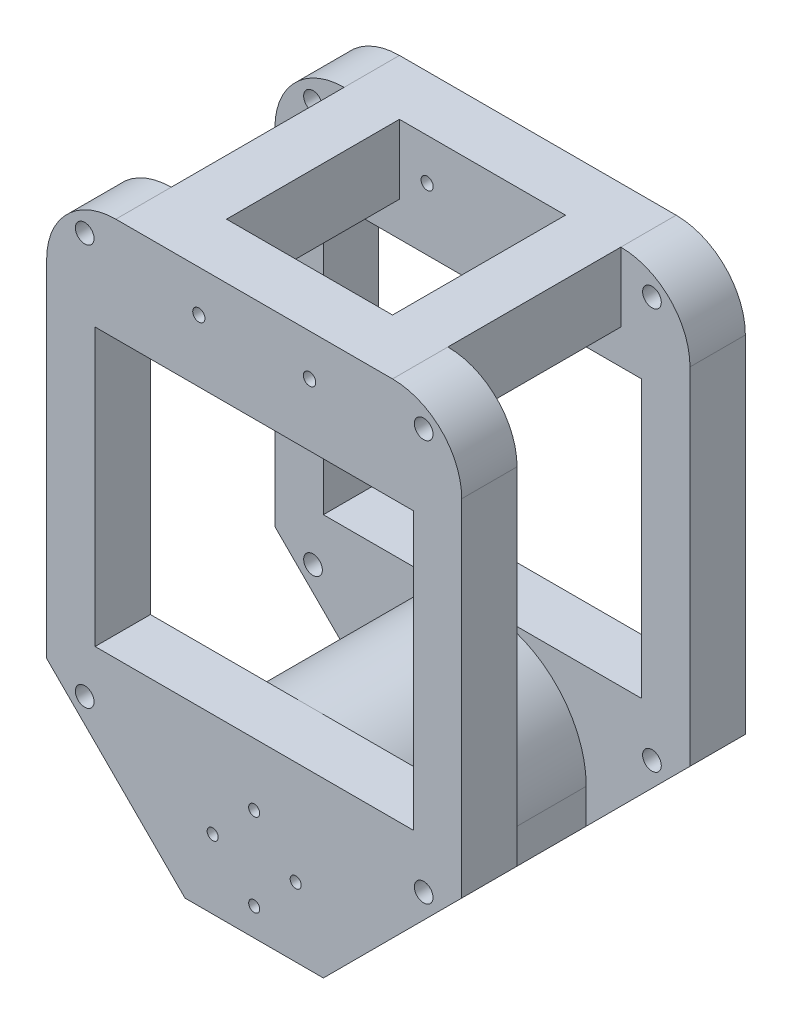
SolidWorks part; units mm, degrees
ref_plane "Front Plane" through (0, 0, 0) normal (0, 0, 1) x (1, 0, 0)
ref_plane "Top Plane" through (0, 0, 0) normal (0, 1, 0) x (1, 0, 0)
ref_plane "Right Plane" through (0, 0, 0) normal (1, 0, 0) x (0, 0, -1)
sketch "Sketch1" plane through (0, 0, 0) normal (0, 0, 1) x (1, 0, 0)
  line L11 (-30, 20.2064) -> (0, 20.2064)
  line L12 (0, 20.2064) -> (30, 20.2064)
  line L13 (30, 20.2064) -> (30, -59.7936)
  line L14 (30, -59.7936) -> (-30, -59.7936)
  line L15 (-30, -59.7936) -> (-30, 20.2064)
  circle A0 centre (-8, 14.2064) radius 0.8836
  circle A1 centre (8, 14.2064) radius 0.8966
  circle A2 centre (0, -49.7936) radius 8 construction
  circle A3 centre (0, -49.7936) radius 6 construction
  circle A4 centre (0, -43.7936) radius 0.8
  circle A5 centre (6, -49.7936) radius 0.8
  circle A6 centre (0, -55.7936) radius 0.8
  circle A7 centre (-6, -49.7936) radius 0.8
  circle A8 centre (-24.5, 16.2064) radius 1.35
  circle A9 centre (24.5, 16.2064) radius 1.35
  circle A10 centre (-24.5, -41.7936) radius 1.35
  circle A11 centre (24.5, -41.7936) radius 1.35
  point P25 (0, -49.7936)
  dimension "D7" = 4
  dimension "D10" = 49
  dimension "D1" = 8
  dimension "D2" = 30
  dimension "D3" = 30
  dimension "D4" = 16
  dimension "D5" = 0
  dimension "D6" = 80
  dimension "D8" = 10
  dimension "D9" = 6
  dimension "D11" = 24.5
  dimension "D12" = 58
  dimension "D13" = 4
extrude "Boss-Extrude1" add sketch "Sketch1" along normal blind 8
sketch "Sketch2" plane through (0, 0, 8) normal (0, 0, 1) x (1, 0, 0)
  line L0 (-12, 20.2064) -> (-12, 10.2064)
  line L1 (30, 20.2064) -> (-30, 20.2064) construction
  line L2 (12, 20.2064) -> (12, 10.2064)
  line L3 (12, 20.2064) -> (20, 20.2064)
  line L4 (20, 20.2064) -> (20, 10.2064)
  line L5 (20, 10.2064) -> (12, 10.2064)
  line L6 (-12, 20.2064) -> (-20, 20.2064)
  line L7 (-20, 20.2064) -> (-20, 10.2064)
  line L8 (-20, 10.2064) -> (-12, 10.2064)
  dimension "D1" = 12
  dimension "D2" = 12
  dimension "D3" = 10
  dimension "D4" = 8
  dimension "D5" = 8
extrude "Boss-Extrude3" add sketch "Sketch2" along normal blind 25
extrude "Boss-Extrude4" add sketch "Sketch1<2>" against normal blind 8 from offset 41
sketch "Sketch1<2>" plane through (0, 0, 0) normal (0, 0, 1) x (1, 0, 0) same geometry as "Sketch1"
sketch "Sketch3" plane through (0, 0, 8) normal (0, 0, 1) x (1, 0, 0)
  line L4 (-30, -59.7936) -> (-10, -59.7936) construction
  line L5 (-6, -49.7936) -> (6, -49.7936) construction
  line L6 (-10, -49.7936) -> (-10, -59.7936)
  line L7 (0, -43.7936) -> (0, -55.7936) construction
  line L8 (10, -49.7936) -> (10, -59.7936)
  line L9 (10, -59.7936) -> (30, -59.7936) construction
  line L10 (-10, -59.7936) -> (10, -59.7936)
  arc A1 (10, -49.7936) -> (-10, -49.7936) centre (0, -49.7936) ccw
extrude "Cut-Extrude1" cut sketch "Sketch3" against normal blind 3
extrude "Cut-Extrude2" cut sketch "Sketch3<2>" along normal blind 3 from surface starting at face at (25.85, -41.7936, 33)
sketch "Sketch3<2>" plane through (0, 0, 8) normal (0, 0, 1) x (1, 0, 0) same geometry as "Sketch3"
sketch "Sketch4" plane through (0, 0, 33) normal (0, 0, -1) x (-1, 0, 0)
  line L0 (-15, -49.7936) -> (-15, -59.7936)
  line L1 (15, -49.7936) -> (15, -59.7936)
  line L2 (-10, -49.7936) -> (-10, -59.7936)
  line L3 (15, -59.7936) -> (30, -59.7936)
  line L4 (-15, -59.7936) -> (-10, -59.7936)
  line L5 (10, -49.7936) -> (10, -59.7936)
  line L6 (-15, -59.7936) -> (-10, -59.7936)
  line L7 (10, -59.7936) -> (15, -59.7936)
  line L8 (15, -59.7936) -> (10, -59.7936)
  line L10 (-15, -59.7936) -> (-10, -59.7936)
  line L11 (10, -59.7936) -> (15, -59.7936)
  line L15 (-30, -59.7936) -> (-10, -59.7936)
  line L16 (-10, -59.7936) -> (-10, -49.7936)
  line L17 (10, -49.7936) -> (10, -59.7936)
  line L18 (10, -59.7936) -> (30, -59.7936)
  line L19 (30, -59.7936) -> (30, 20.2064)
  line L20 (30, 20.2064) -> (20, 20.2064)
  line L21 (20, 20.2064) -> (20, 10.2064)
  line L22 (20, 10.2064) -> (12, 10.2064)
  line L23 (12, 10.2064) -> (12, 20.2064)
  line L24 (12, 20.2064) -> (-12, 20.2064)
  line L25 (-12, 20.2064) -> (-12, 10.2064)
  line L26 (-12, 10.2064) -> (-20, 10.2064)
  line L27 (-20, 10.2064) -> (-20, 20.2064)
  line L28 (-20, 20.2064) -> (-30, 20.2064)
  line L29 (-30, 20.2064) -> (-30, -59.7936)
  line L30 (-30, -59.7936) -> (-15, -59.7936)
  line L34 (30, -59.7936) -> (30, 20.2064)
  line L35 (30, 20.2064) -> (20, 20.2064)
  line L36 (20, 20.2064) -> (20, 10.2064)
  line L37 (20, 10.2064) -> (12, 10.2064)
  line L38 (12, 10.2064) -> (12, 20.2064)
  line L39 (12, 20.2064) -> (-12, 20.2064)
  line L40 (-12, 20.2064) -> (-12, 10.2064)
  line L41 (-12, 10.2064) -> (-20, 10.2064)
  line L42 (-20, 10.2064) -> (-20, 20.2064)
  line L43 (-20, 20.2064) -> (-30, 20.2064)
  line L44 (-30, 20.2064) -> (-30, -59.7936)
  arc A0 (15, -49.7936) -> (-15, -49.7936) centre (0, -49.7936) ccw
  arc A1 (10, -49.7936) -> (-10, -49.7936) centre (0, -49.7936) ccw
  arc A2 (10, -49.7936) -> (-10, -49.7936) centre (0, -49.7936) ccw
  arc A3 (10, -49.7936) -> (-10, -49.7936) centre (0, -49.7936) ccw
  arc A4 (-10, -49.7936) -> (9.3304, -53.3913) centre (0, -49.7936) cw
  dimension "D1" = 0
sketch "Sketch5" plane through (0, 0, 33) normal (0, 0, -1) x (-1, 0, 0)
  line L0 (-15, -49.7936) -> (-15, -59.7936)
  line L1 (-15, -59.7936) -> (-10, -59.7936)
  line L2 (-10, -59.7936) -> (-10, -49.7936)
  line L3 (10, -49.7936) -> (10, -59.7936)
  line L4 (10, -59.7936) -> (15, -59.7936)
  line L5 (15, -59.7936) -> (15, -49.7936)
  arc A0 (10, -49.7936) -> (-10, -49.7936) centre (0, -49.7936) ccw
  arc A1 (15, -49.7936) -> (-15, -49.7936) centre (0, -49.7936) ccw
extrude "Boss-Extrude5" add sketch "Sketch5" along normal blind 25
sketch "Sketch7" plane through (0, 0, 41) normal (0, 0, 1) x (1, 0, 0)
  line L1 (30, 20.2064) -> (30, -59.7936) construction
  line L2 (30, -39.7936) -> (30, -59.7936)
  line L6 (-30, -59.7936) -> (-30, 20.2064) construction
  line L7 (-30, -39.7936) -> (-30, -59.7936)
  line L8 (-30, -39.7936) -> (-10, -59.7936)
  line L9 (10, -59.7936) -> (30, -39.7936)
  line L10 (-30, -59.7936) -> (-10, -59.7936)
  line L11 (10, -59.7936) -> (30, -59.7936)
  dimension "D1" = 20
extrude "Cut-Extrude3" cut sketch "Sketch7" against normal blind 41
fillet "Fillet5" radius 10 4 edges at (-30, 20.2064, 37) (-30, 20.2064, 4) (30, 20.2064, 4) (30, 20.2064, 37)
sketch "Sketch8" plane through (0, 0, 41) normal (0, 0, 1) x (1, 0, 0)
  line L0 (20, 20.2064) -> (-20, 20.2064) construction
  line L1 (-23, 5.2064) -> (23, 5.2064)
  line L2 (-23, 5.2064) -> (-23, -34.7936)
  line L3 (-23, -34.7936) -> (23, -34.7936)
  line L4 (23, 5.2064) -> (23, -34.7936)
  dimension "D1" = 46
  dimension "D2" = 23
  dimension "D3" = 15
  dimension "D4" = 40
extrude "Cut-Extrude4" cut sketch "Sketch8" against normal through all
